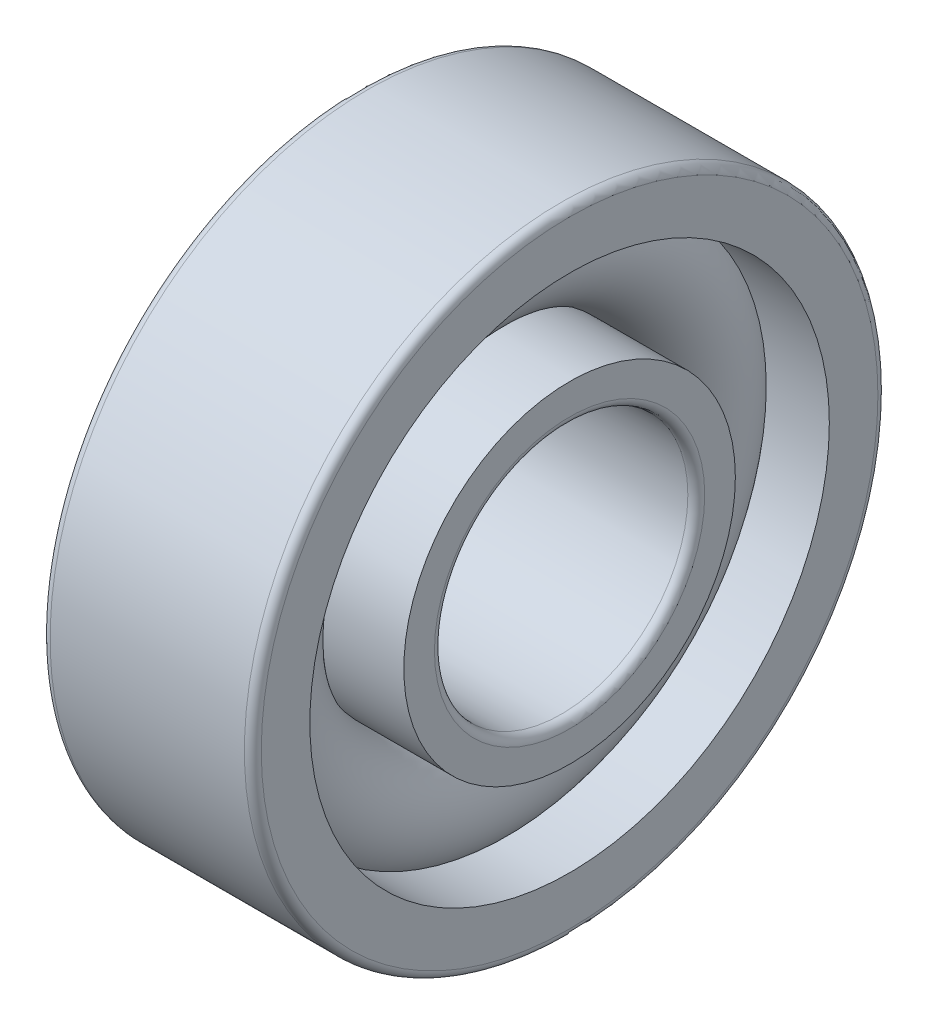
SolidWorks part; units mm, degrees
material "Malleable Cast Iron"
ref_plane "Plane1" through (0, 0, 0) normal (0, 0, 1) x (1, 0, 0)
ref_plane "Plane2" through (0, 0, 0) normal (0, 1, 0) x (1, 0, 0)
ref_plane "Plane3" through (0, 0, 0) normal (1, 0, 0) x (0, 0, -1)
sketch "Clipboard" plane through (0, 0, 0) normal (0, 0, 1) x (1, 0, 0)
  line L0 (-10, 0) -> (10, 0) construction
  line L1 (0, 0) -> (22.3471, -0.7804)
  line L2 (0, 0) -> (5.2468, 0.1832)
  line L3 (0, 0) -> (22.3471, -0.7804)
  line L4 (0, 0) -> (-22.3573, -0.3902)
  dimension "BallCLRad" = 5.25
sketch "CagSpiSke" plane through (0, 0, 0) normal (0, 0, 1) x (1, 0, 0)
  line L0 (0.3375, 5.025) -> (0.3375, 5.475)
  line L1 (0.3375, 5.475) -> (-0.3375, 5.475)
  line L2 (-0.3375, 5.475) -> (-0.3375, 5.025)
  line L3 (-0.3375, 5.025) -> (0.3375, 5.025)
  line L4 (-20.6375, 0) -> (20.6375, 0) construction
  line L5 (0, 0) -> (0, 23.7692) construction
  dimension "OD" = 10.95
  dimension "ID" = 10.05
revolve "CageSpine" add sketch "CagSpiSke" angle 0.001 about L4
ref_axis "Axis1" through (-50, 0, 0) along (1, 0, 0)
sketch "CagBalSke" plane through (0, 0, 0) normal (0, 0, 1) x (1, 0, 0)
  line L0 (-1.485, 5.25) -> (1.485, 5.25)
  line L1 (-1.905, 5.25) -> (1.905, 5.25) construction
  line L2 (-10, 0) -> (10, 0) construction
  line L3 (0, 0) -> (0, 24) construction
  arc A0 (1.485, 5.25) -> (-1.485, 5.25) centre (0, 5.25) cw
  dimension "BallCLRad" = 5.25
revolve "CageBall" [suppressed] add sketch "CagBalSke" angle 360 about L1 reverse direction yes
pattern_circular "CageBalls" [suppressed] count 2 every 180 about axis through (-50, 0, 0) along (1, 0, 0)
sketch "CagTrmODSke" plane through (0, 0, 0) normal (0, 0, 1) x (1, 0, 0)
  line L0 (1.486, 5.475) -> (1.486, 6.736)
  line L1 (1.486, 6.736) -> (-1.486, 6.736)
  line L2 (-1.486, 6.736) -> (-1.486, 5.475)
  line L3 (-1.486, 5.475) -> (1.486, 5.475)
  line L4 (-20.6375, 0) -> (20.6375, 0) construction
  line L5 (0, 0) -> (0, 25) construction
  dimension "Width" = 2.972
  dimension "ID" = 10.95
  dimension "OD" = 13.472
revolve "CageTrimOD" [suppressed] cut sketch "CagTrmODSke" angle 360 about L4 reverse direction yes
sketch "CagTrmIDSke" plane through (0, 0, 0) normal (0, 0, 1) x (1, 0, 0)
  line L0 (1.486, 3.766) -> (1.486, 5.025)
  line L1 (1.486, 5.025) -> (-1.486, 5.025)
  line L2 (-1.486, 5.025) -> (-1.486, 3.766)
  line L3 (-1.486, 3.766) -> (1.486, 3.766)
  line L4 (-20.6375, 0) -> (20.6375, 0) construction
  line L5 (0, 0) -> (0, 25) construction
  dimension "Width" = 2.972
  dimension "ID" = 7.532
  dimension "OD" = 10.05
revolve "CageTrimID" [suppressed] cut sketch "CagTrmIDSke" angle 360 about L4 reverse direction yes
sketch "BalSimSke" plane through (0, 0, 0) normal (0, 0, 1) x (1, 0, 0)
  line L0 (-10, 0) -> (10, 0) construction
  line L1 (-10, 5.25) -> (10, 5.25) construction
  line L2 (0, 0) -> (0, 23) construction
  circle A0 centre (0, 5.25) radius 1.35
  dimension "BallCLRad" = 5.25
  dimension "Ball_diameter" = 2.7
revolve "BallsSimplified" add sketch "BalSimSke" angle 360 about L0
sketch "BalDetSke" plane through (0, 0, 0) normal (0, 0, 1) x (1, 0, 0)
  line L0 (-1.35, 5.25) -> (1.35, 5.25)
  line L1 (-1.905, 5.25) -> (1.905, 5.25) construction
  line L2 (0, 0) -> (0, 25) construction
  arc A0 (1.35, 5.25) -> (-1.35, 5.25) centre (0, 5.25) cw
  dimension "BallCLRad" = 5.25
  dimension "Ball_diameter" = 2.7
revolve "BallDetailed" [suppressed] add sketch "BalDetSke" angle 360 about L1 reverse direction yes
sketch "InnRacSke" plane through (0, 0, 0) normal (0, 0, 1) x (1, 0, 0)
  line L0 (-0.9724, 4.35) -> (-2.5, 4.35)
  line L1 (-2.5, 4.35) -> (-2.5, 3.2)
  line L2 (-2.3, 3) -> (2.3, 3)
  line L3 (2.5, 3.2) -> (2.5, 3.925)
  line L4 (0, 3.925) -> (2.5, 3.925)
  line L5 (-20.6375, 0) -> (20.6375, 0) construction
  line L6 (0, 0) -> (0, 30) construction
  arc A0 (-2.5, 3.2) -> (-2.3, 3) centre (-2.3, 3.2) ccw
  arc A1 (2.3, 3) -> (2.5, 3.2) centre (2.3, 3.2) ccw
  arc A2 (0, 3.925) -> (-0.9724, 4.35) centre (0, 5.25) cw
  dimension "BallCLRad" = 5.25
  dimension "Fillet_radius" = 0.2
  dimension "Ball_diameter" = 2.65
  dimension "ID" = 6
  dimension "OD" = 8.7
  dimension "Width" = 5
revolve "InnerRace" add sketch "InnRacSke" angle 360 about L5 reverse direction yes
sketch "OutRacSke" plane through (0, 0, 0) normal (0, 0, 1) x (1, 0, 0)
  line L0 (0, 6.575) -> (-2.5, 6.575)
  line L1 (-2.5, 6.575) -> (-2.5, 7.3)
  line L2 (-2.3, 7.5) -> (2.3, 7.5)
  line L3 (2.5, 7.3) -> (2.5, 6.15)
  line L4 (2.5, 6.15) -> (0.9724, 6.15)
  line L5 (-20.6375, 0) -> (20.6375, 0) construction
  line L6 (0, 0) -> (0, 30) construction
  arc A0 (-2.5, 7.3) -> (-2.3, 7.5) centre (-2.3, 7.3) cw
  arc A1 (2.3, 7.5) -> (2.5, 7.3) centre (2.3, 7.3) cw
  arc A2 (0.9724, 6.15) -> (0, 6.575) centre (0, 5.25) ccw
  dimension "BallCLRad" = 5.25
  dimension "Fillet_radius" = 0.2
  dimension "Ball_diameter" = 2.65
  dimension "Width" = 5
revolve "OuterRace" add sketch "OutRacSke" angle 360 about L5 reverse direction yes
pattern_circular "BallsDetailed" [suppressed] count 2 every 180 about axis through (-50, 0, 0) along (1, 0, 0)
equation "\"BallCLRad@Clipboard\" = ( \"OD@OutRacSke\" + \"ID@InnRacSke\" ) / 4"
equation "\"BallCLRad@BalSimSke\" = \"BallCLRad@Clipboard\""
equation "\"BallCLRad@BalDetSke\" = \"BallCLRad@Clipboard\""
equation "\"BallCLRad@InnRacSke\" = \"BallCLRad@Clipboard\""
equation "\"BallCLRad@OutRacSke\" = \"BallCLRad@Clipboard\""
equation "\"Ball_diameter@InnRacSke\" = \"Ball_diameter@BalDetSke\" - 0.05"
equation "\"Ball_diameter@OutRacSke\" = \"Ball_diameter@BalDetSke\" - 0.05"
equation "\"Ball_diameter@BalSimSke\" = \"Ball_diameter@BalDetSke\""
equation "\"Width@OutRacSke\" = \"Width@InnRacSke\""
equation "\"Fillet_radius@OutRacSke\" = \"Fillet_radius@InnRacSke\""
equation "\"Max_count@Clipboard\" = int( 3.14159265 / atn(( \"Ball_diameter@BalDetSke\" / 2) / sqr( \"BallCLRad@Clipboard\"  *  \"BallCLRad@Clipboard\" - ( \"Ball_diameter@BalDetSke\" / 2) *  ( \"Ball_diameter@BalDetSke\" / 2))))"
equation "\"Max_count@Clipboard\" = ((sgn( \"Max_count@Clipboard\" - \"Count@Clipboard\" )-1)*( \"Max_count@Clipboard\" - \"Count@Clipboard\" ))/-2+ \"Count@Clipboard\""
equation "\"Count@BallsDetailed\" = int( \"Show_count@Clipboard\" ) "
equation "\"Count@BallsDetailed\" = ((sgn( \"Count@BallsDetailed\" - \"Max_count@Clipboard\" )-1)*( \"Count@BallsDetailed\" - \"Max_count@Clipboard\" ))/-2+ \"Max_count@Clipboard\""
equation "\"Count@BallsDetailed\" = ((sgn( \"Count@BallsDetailed\" - \"Min_count@Clipboard\" )+1)*( \"Count@BallsDetailed\" - \"Min_count@Clipboard\"))/2 +\"Min_count@Clipboard\""
equation "\"Angle@BallsDetailed\" = 360.0 / \"Max_count@Clipboard\""
equation "\"BallCLRad@CagBalSke\" = \"BallCLRad@Clipboard\""
equation "\"Count@CageBalls\" = \"Count@BallsDetailed\""
equation "\"Angle@CageBalls\" = \"Angle@BallsDetailed\""
equation "\"Angle@CageSpine\" =  \"Angle@CageBalls\" * ( \"Count@CageBalls\" -1 + int( \"Count@CageBalls\" / \"Max_count@Clipboard\" ) )  + 0.001 -  int( \"Count@CageBalls\" / \"Max_count@Clipboard\" ) * 0.001"
equation "\"Angle@CageSpine\" =  \"Angle@CageSpine\" * int( \"Min_count@Clipboard\" / 2) + int(1 / \"Min_count@Clipboard\")  * 0.001"
equation "\"CageWallOD@CagBalSke\" =  \"Ball_diameter@BalDetSke\" * 1.1"
equation "\"Thickness@CagSpiSke\" =  \"Ball_diameter@BalDetSke\" * 0.25"
equation "\"OD@CagTrmODSke\" = \"BallCLRad@Clipboard\" * 2 + \"CageWallOD@CagBalSke\" + 0.002"
equation "\"ID@CagTrmODSke\" = \"BallCLRad@Clipboard\" * 2 + \"Ball_diameter@BalDetSke\" / 6"
equation "\"OD@CagTrmIDSke\" = \"BallCLRad@Clipboard\" * 2 - \"Ball_diameter@BalDetSke\" / 6"
equation "\"ID@CagTrmIDSke\" = \"BallCLRad@Clipboard\" * 2 - \"CageWallOD@CagBalSke\" + 0.002"
equation "\"OD@CagSpiSke\" = \"ID@CagTrmODSke\""
equation "\"ID@CagSpiSke\" = \"OD@CagTrmIDSke\""
equation "\"Width@CagTrmODSke\" = \"CageWallOD@CagBalSke\" + 0.002"
equation "\"Width@CagTrmIDSke\" = \"CageWallOD@CagBalSke\" + 0.002"
